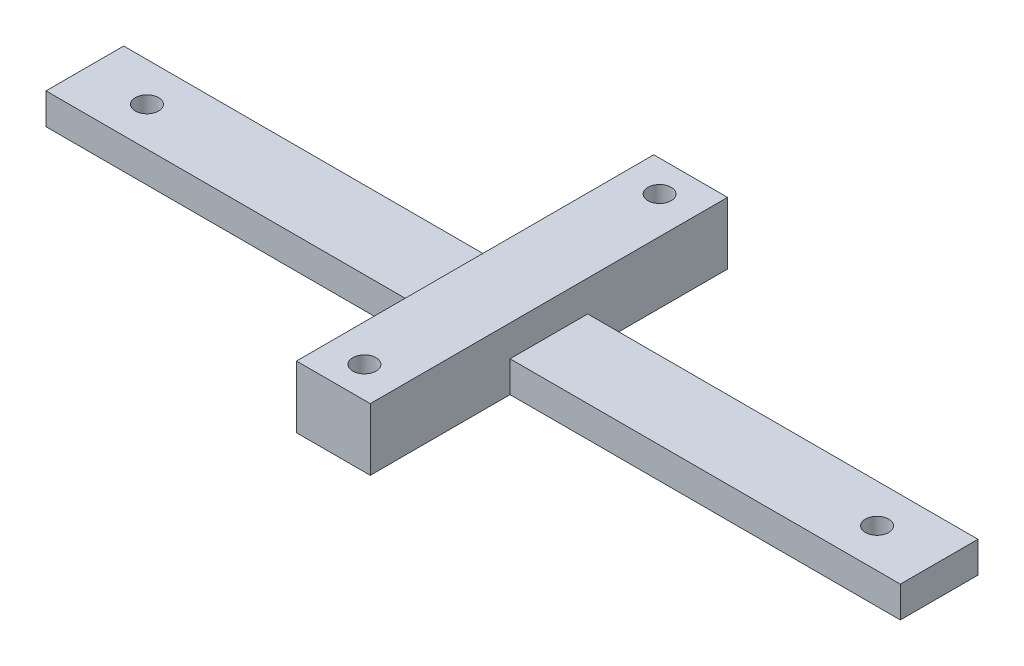
SolidWorks part; units mm, degrees
ref_plane "Front Plane" through (0, 0, 0) normal (0, 0, 1) x (1, 0, 0)
ref_plane "Top Plane" through (0, 0, 0) normal (0, 1, 0) x (1, 0, 0)
ref_plane "Right Plane" through (0, 0, 0) normal (1, 0, 0) x (0, 0, -1)
sketch "Sketch1" plane through (0, 0, 0) normal (0, 1, 0) x (1, 0, 0)
  line L0 (-55, -1.9105) -> (55, -1.9105) construction
  line L1 (-55, -24.9105) -> (4.75, -24.9105)
  line L2 (-55, -6.9105) -> (-55, 3.0895)
  line L3 (-4.75, 21.0895) -> (4.75, 21.0895)
  line L4 (55, -6.9105) -> (55, 3.0895)
  line L5 (-55, -24.9105) -> (55.0673, 24.941) construction
  line L6 (-54.9326, 25.0283) -> (54.9999, -25.0589) construction
  line L7 (-4.75, -24.9105) -> (4.75, -24.9105)
  line L9 (-4.75, 21.0895) -> (4.75, 21.0895)
  line L11 (-4.75, -24.9105) -> (-4.75, -6.9105)
  line L12 (-4.75, -6.9105) -> (-55, -6.9105)
  line L13 (-55, 3.0895) -> (-4.75, 3.0895)
  line L14 (-4.75, 3.0895) -> (-4.75, 21.0895)
  line L15 (4.75, 21.0895) -> (4.75, 3.0895)
  line L16 (4.75, 3.0895) -> (55, 3.0895)
  line L17 (4.75, -24.9105) -> (4.75, -6.9105)
  line L18 (4.75, -6.9105) -> (55, -6.9105)
  line L19 (4.75, 3.0895) -> (-4.75, 3.0895) construction
  line L20 (-4.75, -6.9105) -> (4.75, -6.9105) construction
  line L21 (4.75, -6.9105) -> (4.75, 3.0895) construction
  line L22 (-4.75, 3.0895) -> (-4.75, -6.9105) construction
  line L23 (0, 21.0895) -> (0, -24.9105) construction
  circle A0 centre (-47, -1.9105) radius 1.5
  circle A1 centre (47, -1.9105) radius 1.5
  point P0 (0, 0)
  point P6 (0.0336, -0.0153)
  point P27 (0, 0)
  point P28 (0, 0)
  dimension "D2" = 3
  dimension "D4" = 3
  dimension "D1" = 110
  dimension "D3" = 50
  dimension "D5" = 8
  dimension "D6" = 8
  dimension "D7" = 9.5
  dimension "D8" = 10
  dimension "D9" = 18
extrude "Boss-Extrude1" add sketch "Sketch1" along normal blind 4 contours L17 L18 L4 L16 L15 L3 L14 L13 L2 L12 L11 L1 A1 A0 region at (0, 0, 1.9105)
sketch "Sketch2" plane through (0, 4, 0) normal (0, 1, 0) x (1, 0, 0)
  line L6 (-4.75, 21.0895) -> (4.75, 21.0895)
  line L7 (-4.75, 21.0895) -> (-4.75, -24.9105)
  line L8 (-4.75, -24.9105) -> (4.75, -24.9105)
  line L9 (4.75, 21.0895) -> (4.75, -24.9105)
  point P4 (0, 0)
extrude "Boss-Extrude2" add sketch "Sketch2" along normal blind 4
sketch "Sketch4" plane through (0, 8, 0) normal (0, 1, 0) x (1, 0, 0)
  line L0 (0, 21.0895) -> (0, -24.9105) construction
  line L3 (4.75, 21.0895) -> (-4.75, 21.0895) construction
  line L4 (-4.75, -24.9105) -> (4.75, -24.9105) construction
  circle A0 centre (0, -20.9105) radius 1.5
  circle A1 centre (0, 17.0895) radius 1.5
  point P2 (0, 0)
  point P5 (0, 0)
  dimension "D1" = 3
  dimension "D2" = 3
  dimension "D3" = 4
  dimension "D4" = 4
extrude "Cut-Extrude1" cut sketch "Sketch4" against normal blind 9
